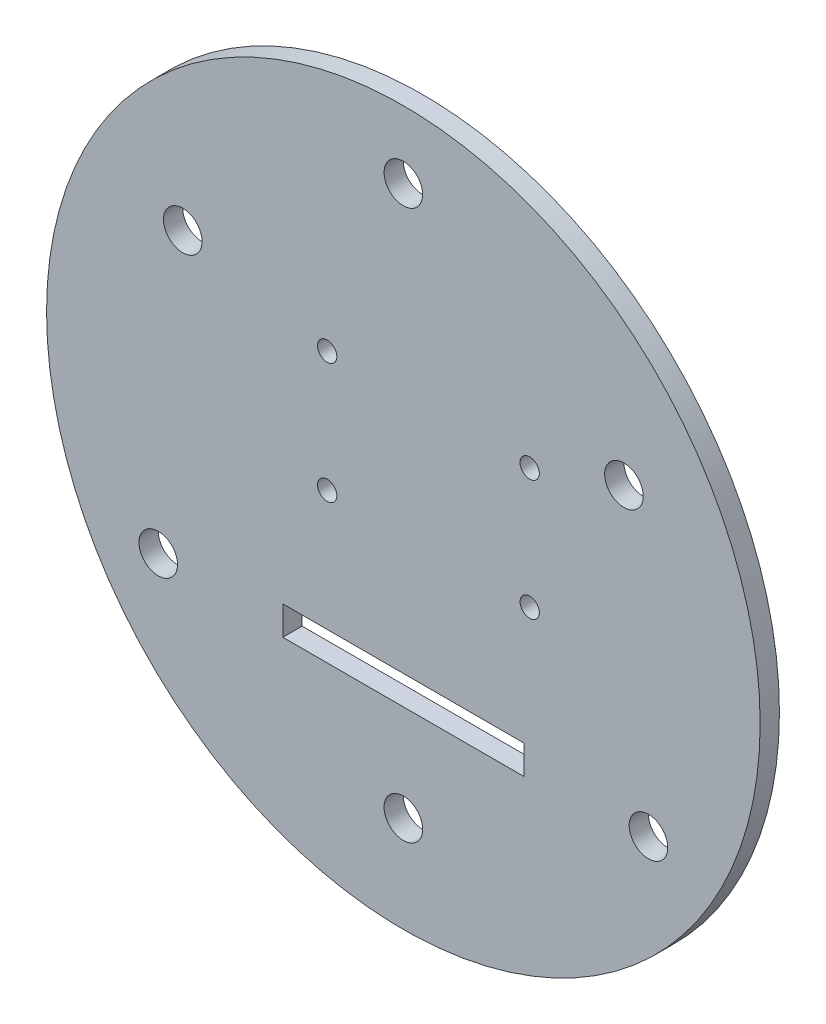
SolidWorks part; units mm, degrees
material "ABS"
ref_plane "Plan de face" through (0, 0, 0) normal (0, 0, 1) x (1, 0, 0)
ref_plane "Plan de dessus" through (0, 0, 0) normal (0, 1, 0) x (1, 0, 0)
ref_plane "Plan de droite" through (0, 0, 0) normal (1, 0, 0) x (0, 0, -1)
sketch "Esquisse1" plane through (0, 0, 0) normal (0, 0, 1) x (1, 0, 0)
  line L0 (0, 0) -> (0, -27) construction
  line L1 (0, -27) -> (0, 30) construction
  line L2 (0, 0) -> (25.4165, -15.9375) construction
  line L3 (25.4165, -15.9375) -> (-22.8748, 14.3437) construction
  line L4 (-25.4165, -15.9375) -> (0, 0) construction
  line L5 (0, 0) -> (22.8748, 14.3437) construction
  line L6 (0, 30) -> (25.4165, -15.9375) construction
  line L8 (12.5, -14) -> (-12.5, -14)
  line L9 (12.5, -14) -> (12.5, -17)
  line L10 (12.5, -17) -> (-12.5, -17)
  line L11 (-12.5, -14) -> (-12.5, -17)
  circle A0 centre (0, 0) radius 37
  circle A1 centre (0, 30) radius 2
  circle A2 centre (-22.8748, 14.3437) radius 2
  circle A3 centre (-25.4165, -15.9375) radius 2
  circle A4 centre (0, -27) radius 2
  circle A5 centre (25.4165, -15.9375) radius 2
  circle A6 centre (22.8748, 14.3437) radius 2
  dimension "D1" = 74
  dimension "D11" = 4
  dimension "D12" = 4
  dimension "D13" = 4
  dimension "D14" = 4
  dimension "D15" = 4
  dimension "D16" = 4
  dimension "D2" = 27
  dimension "D3" = 57
  dimension "D4" = 57
  dimension "D5" = 30
  dimension "D6" = 30
  dimension "D7" = 27
  dimension "D8" = 52.5
  dimension "D9" = 52.5
  dimension "D10" = 47.25
  dimension "D17" = 25
  dimension "D18" = 3
  dimension "D19" = 10
  dimension "D20" = 12.5
extrude "Boss.-Extru.1" add sketch "Esquisse1" along normal blind 2
sketch "Esquisse2" plane through (0, 0, 0) normal (0, 0, -1) x (-1, 0, 0)
  line L0 (-16.55, 14.9) -> (-16.55, -13.5)
  line L1 (-12.55, 14.9) -> (12.55, 14.9)
  line L2 (-12.55, 14.9) -> (-12.55, -9.5)
  line L3 (-12.55, -9.5) -> (12.55, -9.5)
  line L4 (12.55, 14.9) -> (12.55, -9.5)
  line L5 (-16.55, -13.5) -> (16.55, -13.5)
  line L6 (16.55, -13.5) -> (16.55, 14.9)
  line L7 (16.55, 14.9) -> (12.55, 14.9)
  line L8 (-16.55, 14.9) -> (-12.55, 14.9)
  point P0 (0, 0)
  dimension "D1" = 25.1
  dimension "D2" = 9.5
  dimension "D3" = 24.4
  dimension "D4" = 4
  dimension "D5" = 4
  dimension "D6" = 4
  dimension "D7" = 12.55
extrude "Boss.-Extru.2" add sketch "Esquisse2" along normal blind 15 contours L8 L0 L5 L6 L7 L4 L3 L2 region at (14.55, 14.4639, 0)
sketch "Esquisse3" plane through (-12.55, 0, 0) normal (1, 0, 0) x (0, 0, -1)
  line L0 (15, 14.9) -> (0, 14.9) construction
  line L1 (10.625, 14.9) -> (8.625, 14.9)
  line L2 (10.625, 14.9) -> (10.625, -13.5)
  line L3 (10.625, -13.5) -> (8.625, -13.5)
  line L4 (8.625, 14.9) -> (8.625, -13.5)
  line L5 (15, -13.5) -> (0, -13.5) construction
  line L6 (0, 14.9) -> (7.5, 14.9) construction
  line L8 (5.625, 14.9) -> (7.625, 14.9)
  line L9 (5.625, 14.9) -> (5.625, -13.5)
  line L10 (5.625, -13.5) -> (7.625, -13.5)
  line L11 (7.625, 14.9) -> (7.625, -13.5)
  line L12 (8, 14.9) -> (8, -13.5) construction
  dimension "D1" = 2
  dimension "D2" = 0.625
  dimension "D3" = 2
  dimension "D4" = 1
  dimension "D5" = 0.375
  dimension "D6" = 0.5
extrude "Boss.-Extru.3" add sketch "Esquisse3" along normal blind 2.25 contours L11 L10 L9 L8 | L2 L3 L4 L1
sketch "Esquisse5" plane through (12.55, 0, 0) normal (-1, 0, 0) x (0, 0, 1)
  line L1 (-10.625, 14.9) -> (-8.625, 14.9)
  line L2 (-10.625, 14.9) -> (-10.625, -9.5)
  line L3 (-10.625, -9.5) -> (-8.625, -9.5)
  line L4 (-8.625, 14.9) -> (-8.625, -9.5)
  line L5 (-7.625, 14.9) -> (-5.625, 14.9)
  line L6 (-7.625, 14.9) -> (-7.625, -9.5)
  line L7 (-7.625, -9.5) -> (-5.625, -9.5)
  line L8 (-5.625, 14.9) -> (-5.625, -9.5)
extrude "Boss.-Extru.4" add sketch "Esquisse5" along normal blind 2.25
sketch "Esquisse7" plane through (0, 0, -15) normal (0, 0, -1) x (-1, 0, 0)
  line L1 (-16.55, 14.9) -> (16.55, 14.9)
  line L2 (-16.55, 14.9) -> (-16.55, -13.5)
  line L3 (-16.55, -13.5) -> (16.55, -13.5)
  line L4 (16.55, 14.9) -> (16.55, -13.5)
extrude "Boss.-Extru.5" add sketch "Esquisse7" against normal blind 1
sketch "Esquisse8" plane through (0, 0, -15) normal (0, 0, -1) x (-1, 0, 0)
  line L1 (-7.5, 7.5) -> (7.5, 7.5)
  line L2 (-7.5, 7.5) -> (-7.5, -7.5)
  line L3 (-7.5, -7.5) -> (7.5, -7.5)
  line L4 (7.5, 7.5) -> (7.5, -7.5)
  line L5 (-7.5, 7.5) -> (7.5, -7.5) construction
  line L6 (-7.5, -7.5) -> (7.5, 7.5) construction
  point P0 (0, 0)
  dimension "D1" = 15
  dimension "D2" = 15
extrude "Enlèv. mat.-Extru.1" cut sketch "Esquisse8" against normal blind 3 contours L3 L4 L1 L2
sketch "Esquisse9" plane through (0, -13.5, 0) normal (0, -1, 0) x (1, 0, 0)
  line L0 (16.55, 0) -> (-16.55, 0) construction
  line L1 (-10.5, -4.4) -> (10.5, -4.4)
  line L2 (-10.5, -4.4) -> (-10.5, -6.9)
  line L3 (-10.5, -6.9) -> (10.5, -6.9)
  line L4 (10.5, -4.4) -> (10.5, -6.9)
  line L6 (10.5, -4.4) -> (10.5, 0) construction
  line L7 (10.5, 0) -> (-10.5, 0) construction
  line L8 (-10.5, 0) -> (-10.5, -4.4) construction
  point P6 (0, -4.4)
  dimension "D1" = 21
  dimension "D2" = 2.5
  dimension "D3" = 4.4
  dimension "D4" = 0
extrude "Enlèv. mat.-Extru.2" cut sketch "Esquisse9" against normal blind 3 contours L1 L4 L3 L2
sketch "Esquisse10" plane through (0, 0, 2) normal (0, 0, 1) x (1, 0, 0)
  line L0 (16.55, -13.5) -> (-16.55, -13.5) construction
  line L1 (-16.55, -13.5) -> (-16.55, 14.9) construction
  line L2 (16.55, 14.9) -> (16.55, -13.5) construction
  line L3 (16.55, 14.9) -> (12.55, 14.9) construction
  line L4 (-16.55, 14.9) -> (-12.55, 14.9) construction
  circle A0 centre (-14.55, 8.9) radius 1
  circle A1 centre (-14.55, -11.5) radius 1
  circle A2 centre (14.55, -11.5) radius 1
  circle A3 centre (14.55, 8.9) radius 1
  dimension "D1" = 2
  dimension "D2" = 2
  dimension "D3" = 2
  dimension "D4" = 2
  dimension "D5" = 2
  dimension "D6" = 2
  dimension "D7" = 2
  dimension "D8" = 2
  dimension "D9" = 2
  dimension "D10" = 6
  dimension "D11" = 6
  dimension "D12" = 2
sketch "Esquisse11" plane through (0, 0, -15) normal (0, 0, -1) x (-1, 0, 0)
  line L1 (16.55, 14.9) -> (-16.55, 14.9)
  line L2 (16.55, 14.9) -> (16.55, -13.5)
  line L3 (16.55, -13.5) -> (-16.55, -13.5)
  line L4 (-16.55, 14.9) -> (-16.55, -13.5)
extrude "Enlèv. mat.-Extru.4" cut sketch "Esquisse11" against normal blind 15
sketch "Sketch1" plane through (0, 0, 0) normal (0, 0, -1) x (-1, 0, 0)
  line L1 (-6.6, -5.5) -> (1.4, -5.5) construction
  line L2 (-6.6, -5.5) -> (-6.6, 2.5) construction
  line L3 (-6.6, 2.5) -> (1.4, 2.5) construction
  line L4 (1.4, -5.5) -> (1.4, 2.5) construction
  line L5 (-6.6, -5.5) -> (1.4, 2.5) construction
  line L6 (-6.6, 2.5) -> (1.4, -5.5) construction
  line L7 (-13.1, -1.5) -> (7.9, -1.5) construction
  line L8 (-13.1, -1.5) -> (-13.1, 11) construction
  line L9 (-13.1, 11) -> (7.9, 11) construction
  line L10 (7.9, -1.5) -> (7.9, 11) construction
  line L11 (-13.1, -1.5) -> (7.9, 11) construction
  line L12 (-13.1, 11) -> (7.9, -1.5) construction
  circle A0 centre (0, 0) radius 37
  circle A1 centre (0, 0) radius 39.3 construction
  circle A2 centre (0, 0) radius 37 construction
  circle A3 centre (7.9, -1.5) radius 1
  circle A4 centre (-13.1, -1.5) radius 1
  circle A5 centre (-13.1, 11) radius 1.75
  circle A6 centre (7.9, 11) radius 1
  circle A7 centre (-13.1, -1.5) radius 1.75
  circle A8 centre (-13.1, 11) radius 1
  circle A9 centre (7.9, 11) radius 1.75
  circle A10 centre (7.9, -1.5) radius 1.75
  point P11 (0, 0)
  point P22 (-2.6, 4.75)
  point P33 (-2.6, -1.5)
  dimension "D3" = 2
  dimension "D6" = 2
  dimension "D7" = 2
  dimension "D8" = 3.5
  dimension "D9" = 3.5
  dimension "D10" = 2
  dimension "D11" = 3.5
  dimension "D12" = 3.5
  dimension "D1" = 8
  dimension "D2" = 8
  dimension "D4" = 21
  dimension "D5" = 12.5
  dimension "D13" = 2.6
  dimension "D14" = 1.5
extrude "Boss-Extrude1" add sketch "Sketch1" along normal blind 10 contours A10 A3 | A9 A6 | A5 A8 | A7 A4 region at (14.8005, 11, 0) region at (14.8005, -1.5, 0) region at (-6.1995, 11, 0) region at (-6.1995, -1.5, 0)
extrude "Cut-Extrude1" cut sketch "Sketch1<3>" against normal blind 10 contours A8 | A4 | A3 | A6 region at (-7.9, -1.5, 0) region at (13.1, -1.5, 0) region at (-7.9, 11, 0) region at (13.1, 11, 0)
sketch "Sketch1<3>" plane through (0, 0, 0) normal (0, 0, -1) x (-1, 0, 0) same geometry as "Sketch1"
